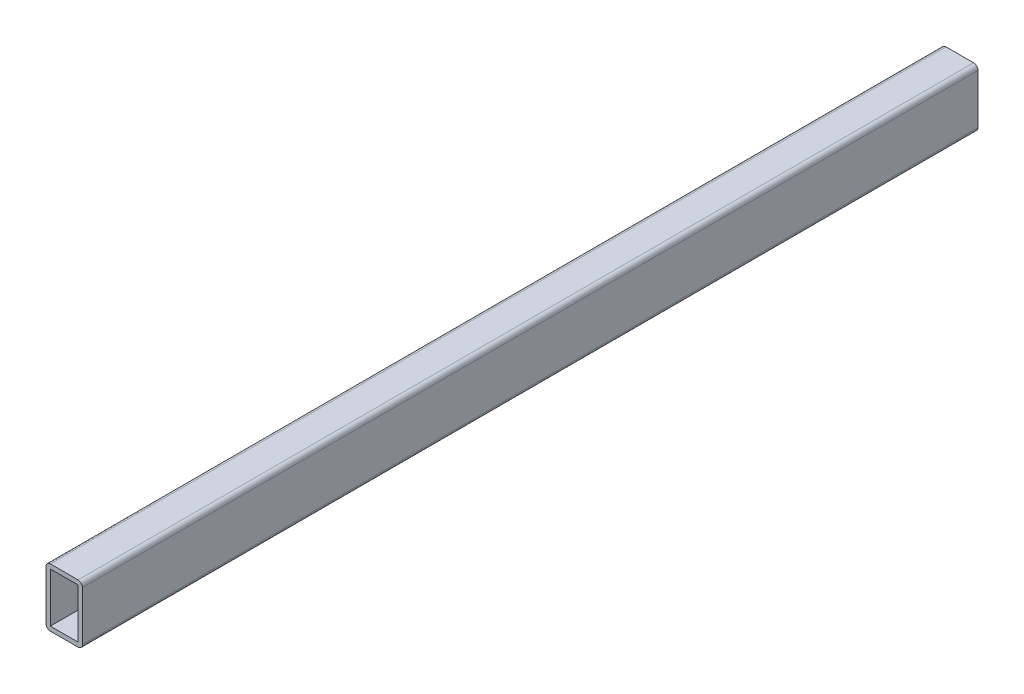
SolidWorks part; units mm, degrees
ref_plane "Front Plane" through (0, 0, 0) normal (0, 0, 1) x (1, 0, 0)
ref_plane "Top Plane" through (0, 0, 0) normal (0, 1, 0) x (1, 0, 0)
ref_plane "Right Plane" through (0, 0, 0) normal (1, 0, 0) x (0, 0, -1)
sketch "Sketch1" plane through (0, 0, 0) normal (0, 0, 1) x (1, 0, 0)
  line L0 (19, 34) -> (-19, 34)
  line L1 (19, -40) -> (-19, -40)
  line L2 (25, -34) -> (25, 34)
  line L3 (19, 40) -> (-19, 40)
  line L4 (-25, -34) -> (-25, 34)
  line L5 (25, -40) -> (-25, 40) construction
  line L6 (25, 40) -> (-25, -40) construction
  line L7 (-19, -34) -> (-19, 34)
  line L8 (19, -34) -> (-19, -34)
  line L9 (19, -34) -> (19, 34)
  arc A0 (-19, -40) -> (-25, -34) centre (-19, -34) cw
  arc A1 (19, -40) -> (25, -34) centre (19, -34) ccw
  arc A2 (25, 34) -> (19, 40) centre (19, 34) ccw
  arc A3 (-19, 40) -> (-25, 34) centre (-19, 34) ccw
  arc A4 (-19, 34) -> (-19, 34) centre (-19, 34) ccw
  arc A5 (-19, -34) -> (-19, -34) centre (-19, -34) cw
  arc A6 (19, -34) -> (19, -34) centre (19, -34) ccw
  arc A7 (19, 34) -> (19, 34) centre (19, 34) ccw
  point P0 (0, 0)
  dimension "D1" = 6
  dimension "D3" = 80
  dimension "D4" = 50
  dimension "D2" = 6
extrude "Boss-Extrude1" add sketch "Sketch1" along normal mid plane 1230
equation "\"M5_tap\"=4.2mm"
equation "\"M5_clearence\"=5.5mm"
equation "\"M6_tap\"=5mm"
equation "\"M6_clearence\"=6.6mm"
equation "\"work_area_width\"=1100mm"
equation "\"work_area_depth\"=900mm"
equation "\"D3@Sketch1\"=\"steel_gantry_width\""
equation "\"D4@Sketch1\"=\"steel_gantry_height\""
equation "\"D1@Sketch1\"=\"steel_gantry_radius\""
equation "\"D2@Sketch1\"=\"steel_gantry_wall_thickness\""
equation "\"D1@Boss-Extrude1\"=\"work_area_width\" + \"steel_sides_height\" + \"steel_rollers_width\""
equation "\"steel_base_width\"=80mm"
equation "\"steel_base_height\"=50mm"
equation "\"steel_base_wall_thickness\"=3mm"
equation "\"steel_base_radius\"=6mm"
equation "\"steel_sides_width\"=80mm"
equation "\"steel_sides_height\"=50mm"
equation "\"steel_sides_wall_thickness\"=5mm"
equation "\"steel_sides_radius\"=6mm"
equation "\"steel_gantry_width\"=80mm"
equation "\"steel_gantry_height\"=50mm"
equation "\"steel_gantry_wall_thickness\"=6mm"
equation "\"steel_gantry_radius\"=6mm"
equation "\"steel_rollers_width\"=80mm"
equation "\"steel_rollers_height\"=50mm"
equation "\"steel_rollers_wall_thickness\"=6mm"
equation "\"steel_rollers_radius\"=6mm"
equation "\"steel_zbox_width\"=80mm"
equation "\"steel_zbox_height\"=50mm"
equation "\"steel_zbox_wall_thickness\"=3mm"
equation "\"steel_zbox_radius\"=6mm"
